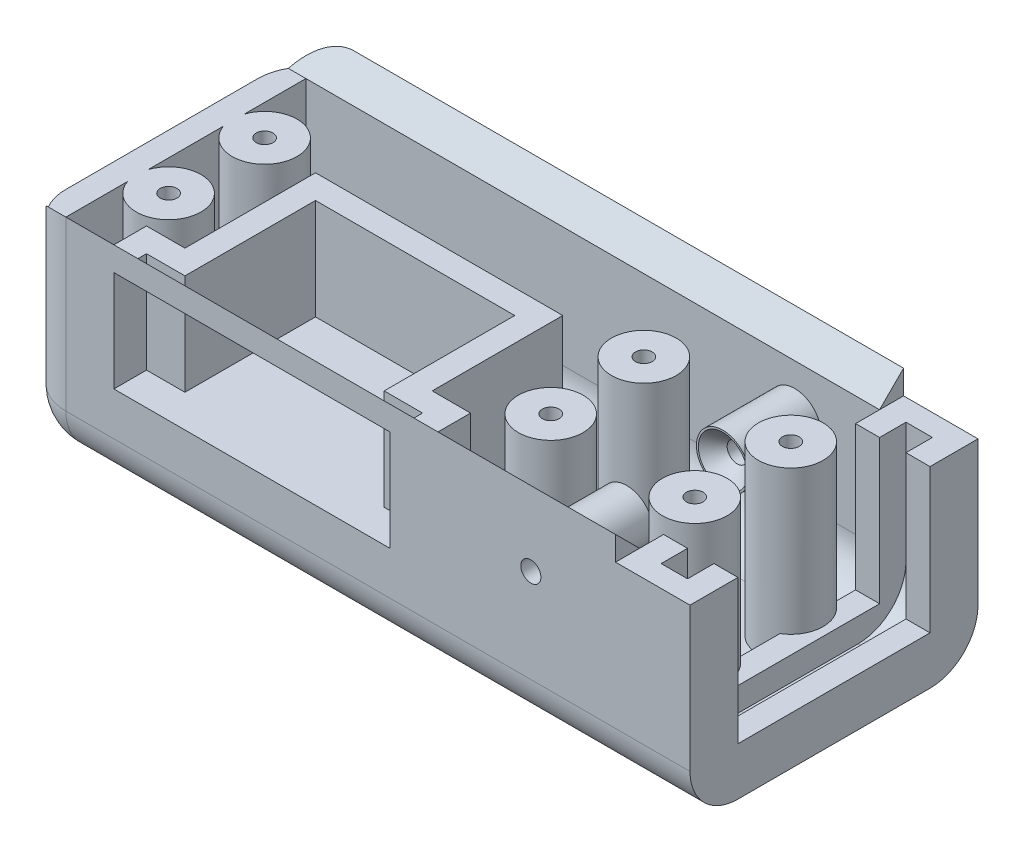
SolidWorks part; units mm, degrees
ref_plane "Front Plane" through (0, 0, 0) normal (0, 0, 1) x (1, 0, 0)
ref_plane "Top Plane" through (0, 0, 0) normal (0, 1, 0) x (1, 0, 0)
ref_plane "Right Plane" through (0, 0, 0) normal (1, 0, 0) x (0, 0, -1)
sketch "Sketch1" plane through (0, 0, 0) normal (0, 1, 0) x (1, 0, 0)
  line L0 (0, 0) -> (20, 0)
  line L1 (140, 0) -> (140, 10)
  line L2 (140, 10) -> (135, 10)
  line L3 (135, 10) -> (135, 4.5)
  line L4 (135, 4.5) -> (129.5, 4.5)
  line L5 (129.5, 4.5) -> (129.5, 10)
  line L6 (129.5, 10) -> (124.5, 10)
  line L7 (124.5, 10) -> (124.5, 5)
  line L8 (124.5, 5) -> (82.5, 5)
  line L14 (5, 55) -> (124.5, 55)
  line L15 (124.5, 55) -> (124.5, 50)
  line L16 (124.5, 50) -> (129.5, 50)
  line L17 (129.5, 50) -> (129.5, 55.5)
  line L18 (129.5, 55.5) -> (135, 55.5)
  line L19 (135, 55.5) -> (135, 50)
  line L20 (135, 50) -> (140, 50)
  line L21 (140, 50) -> (140, 60)
  line L22 (140, 60) -> (0, 60)
  line L23 (0, 60) -> (0, 0)
  line L24 (82.5, 5) -> (82.5, 11.8)
  line L25 (82.5, 11.8) -> (74.5, 11.8)
  line L26 (74.5, 11.8) -> (74.5, 39)
  line L27 (74.5, 39) -> (23, 39)
  line L28 (23, 39) -> (23, 11.8)
  line L29 (23, 11.8) -> (15, 11.8)
  line L30 (15, 11.8) -> (15, 5)
  line L31 (15, 5) -> (5, 5)
  line L33 (5, 55) -> (5, 5)
  line L34 (20, 0) -> (20, 6.8)
  line L35 (20, 6.8) -> (28, 6.8)
  line L36 (28, 6.8) -> (28, 34)
  line L37 (28, 34) -> (69.5, 34)
  line L38 (69.5, 34) -> (69.5, 6.8)
  line L39 (69.5, 6.8) -> (77.5, 6.8)
  line L40 (77.5, 6.8) -> (77.5, 0)
  line L41 (77.5, 0) -> (140, 0)
  dimension "D1" = 140
  dimension "D2" = 10
  dimension "D3" = 5
  dimension "D4" = 5.5
  dimension "D5" = 5.5
  dimension "D6" = 5
  dimension "D7" = 5
  dimension "D8" = 5
  dimension "D9" = 5
  dimension "D10" = 5.5
  dimension "D11" = 5
  dimension "D12" = 10
  dimension "D13" = 40
  dimension "D14" = 5.5
  dimension "D15" = 5.5
  dimension "D16" = 5
  dimension "D17" = 6.8
  dimension "D18" = 8
  dimension "D19" = 27.2
  dimension "D20" = 41.5
  dimension "D21" = 5
  dimension "D22" = 10
  dimension "D23" = 27.2
  dimension "D24" = 8
  dimension "D25" = 15
  dimension "D26" = 5
  dimension "D27" = 5
  dimension "D28" = 5
  dimension "D29" = 5
  dimension "D30" = 5
  dimension "D31" = 5
  dimension "D32" = 5
extrude "Boss-Extrude1" add sketch "Sketch1" along normal blind 35
sketch "Sketch2" plane through (0, 0, 0) normal (0, -1, 0) x (-1, 0, 0)
  line L1 (0, 0) -> (-140, 0)
  line L2 (0, 0) -> (0, 60)
  line L3 (0, 60) -> (-140, 60)
  line L4 (-140, 0) -> (-140, 60)
extrude "Boss-Extrude2" add sketch "Sketch2" along normal blind 5
sketch "Sketch3" plane through (0, 0, 0) normal (0, 1, 0) x (1, 0, 0)
  line L0 (124.5, 50) -> (124.5, 10)
  line L1 (124.5, 10) -> (129.5, 10)
  line L2 (129.5, 10) -> (129.5, 50)
  line L3 (129.5, 50) -> (124.5, 50)
  line L4 (135, 50) -> (140, 50)
  line L5 (140, 50) -> (140, 10)
  line L6 (140, 10) -> (135, 10)
  line L7 (135, 10) -> (135, 50)
extrude "Boss-Extrude3" add sketch "Sketch3" along normal blind 5
fillet "Fillet1" radius 10 6 edges at (10, 0, -5) (103.5, 0, -5) (132.25, 0, -4.5) (132.25, 0, -55.5) (64.75, 0, -55) (70, -5, -60)
sketch "Sketch4" plane through (0, 0, 0) normal (-1, 0, 0) x (0, 0, 1)
  line L0 (0, 35) -> (0, 40)
  line L1 (0, 35) -> (-5, 35)
  line L2 (-60, 35) -> (0, 35) construction
  line L3 (-5, 35) -> (0, 40)
  line L4 (-55, 35) -> (-60, 35)
  line L5 (-60, 35) -> (-60, 40)
  line L6 (-60, 40) -> (-55, 35)
  dimension "D1" = 5
  dimension "D2" = 5
  dimension "D3" = 5
  dimension "D4" = 5
extrude "Boss-Extrude4" add sketch "Sketch4" against normal offset from surface (124.5 mm away) 15.5 up to face at (140, 15.881, -32.4523)
sketch "Sketch5" plane through (0, 0, 0) normal (0, 1, 0) x (1, 0, 0)
  line L0 (28, 34) -> (69.5, 34)
  line L1 (69.5, 34) -> (69.5, 6.8)
  line L2 (69.5, 6.8) -> (77.5, 6.8)
  line L3 (77.5, 6.8) -> (77.5, 0)
  line L4 (77.5, 0) -> (20, 0)
  line L5 (124.5, 0) -> (0, 0) construction
  line L6 (20, 0) -> (20, 6.8)
  line L7 (20, 6.8) -> (28, 6.8)
  line L8 (28, 6.8) -> (28, 34)
extrude "Boss-Extrude5" add sketch "Sketch5" along normal blind 14
fillet "Fillet2" radius 10 1 edges at (70, -5, 0)
sketch "Sketch6" plane through (0, 0, 0) normal (0, 1, 0) x (1, 0, 0)
  line L0 (140, 50) -> (140, 10) construction
  circle A0 centre (11.3966, 20) radius 6.75
  circle A1 centre (11.3966, 20) radius 1.75
  point P0 (11.3966, 20)
  point P1 (11.3966, 40)
  point P2 (121, 40)
  point P3 (121, 20)
  point P4 (91, 20)
  point P5 (90.3923, 40)
  dimension "D5" = 3.5
  dimension "D6" = 13.5
  dimension "D1" = 11.3966
  dimension "D2" = 20
  dimension "D3" = 19
  dimension "D4" = 20
  dimension "D7" = 30
sketch "Sketch7" plane through (0, 0, 0) normal (0, 0, 1) x (1, 0, 0)
  line L0 (0, 40) -> (0, 5) construction
  line L2 (0, 5) -> (140, 5) construction
  point P0 (106.85, 24.5)
  dimension "D1" = 106.85
  dimension "D2" = 19.5
hole_wizard "M5 Tapped Hole1" positions "Sketch8" profile "Sketch10" tap size "M5" standard "AS" end condition through all
sketch "Sketch8" plane through (0, 0, 0) normal (0, 0, 1) x (1, 0, 0)
  point P0 (106.85, 24.5)
sketch "Sketch10" plane through (106.85, 24.5, 0) normal (1, 0, 0) x (0, -1, 0)
  line L0 (0, 0) -> (0, 60)
  line L1 (0, 60) -> (2.1, 60)
  line L2 (2.1, 60) -> (2.1, 0)
  line L5 (2.1, 0) -> (0, 0)
  line L11 (0, -6.35) -> (0, 107.95) construction
  dimension "Thru Tap Drill Dia." = 4.2
  dimension "Thru Tap Drill Depth" = 60
cosmetic thread "Hole Thread1" parameters "D2"=5
extrude "Boss-Extrude6" add sketch "Sketch6" along normal up to surface (35 mm away) up to face at (2.5, 35, -30)
pattern_sketch "Sketch-Pattern1" of "Boss-Extrude6" driven by "Sketch6"
ref_plane "Plane1" through (0, 0, -30) normal (0, 0, 1) x (1, 0, 0)
sketch "Sketch12" plane through (0, 0, -5) normal (0, 0, -1) x (-1, 0, 0)
  circle A0 centre (-106.85, 24.5) radius 5.5
  circle A1 centre (-106.85, 24.5) radius 2.1
  dimension "D1" = 4.2
  dimension "D2" = 11
extrude "Boss-Extrude7" add sketch "Sketch12" along normal blind 15
mirror "Mirror1" about plane through (0, 0, -30) normal (0, 0, 1) of "Boss-Extrude7"
cosmetic thread "Hole Thread2" parameters "D2"=5
chamfer "Chamfer2" distance 3 angle 45 2 edges at (104.75, 24.5, -40) (104.75, 24.5, -20)
sketch "Sketch14" plane through (0, 0, 0) normal (0, 1, 0) x (1, 0, 0)
  circle A0 centre (11.3966, 20) radius 1.75
  point P3 (0, 0)
  dimension "D1" = 3.5
extrude "Cut-Extrude1" cut sketch "Sketch14" against normal blind 15
pattern_sketch "Sketch-Pattern2" of "Cut-Extrude1" driven by "Sketch6"
fillet "Fillet3" radius 10 5 edges at (0, 22.5, -60) (0, -2.0711, -57.0711) (0, -5, -30) (0, -2.0711, -2.9289) (0, 22.5, 0)
